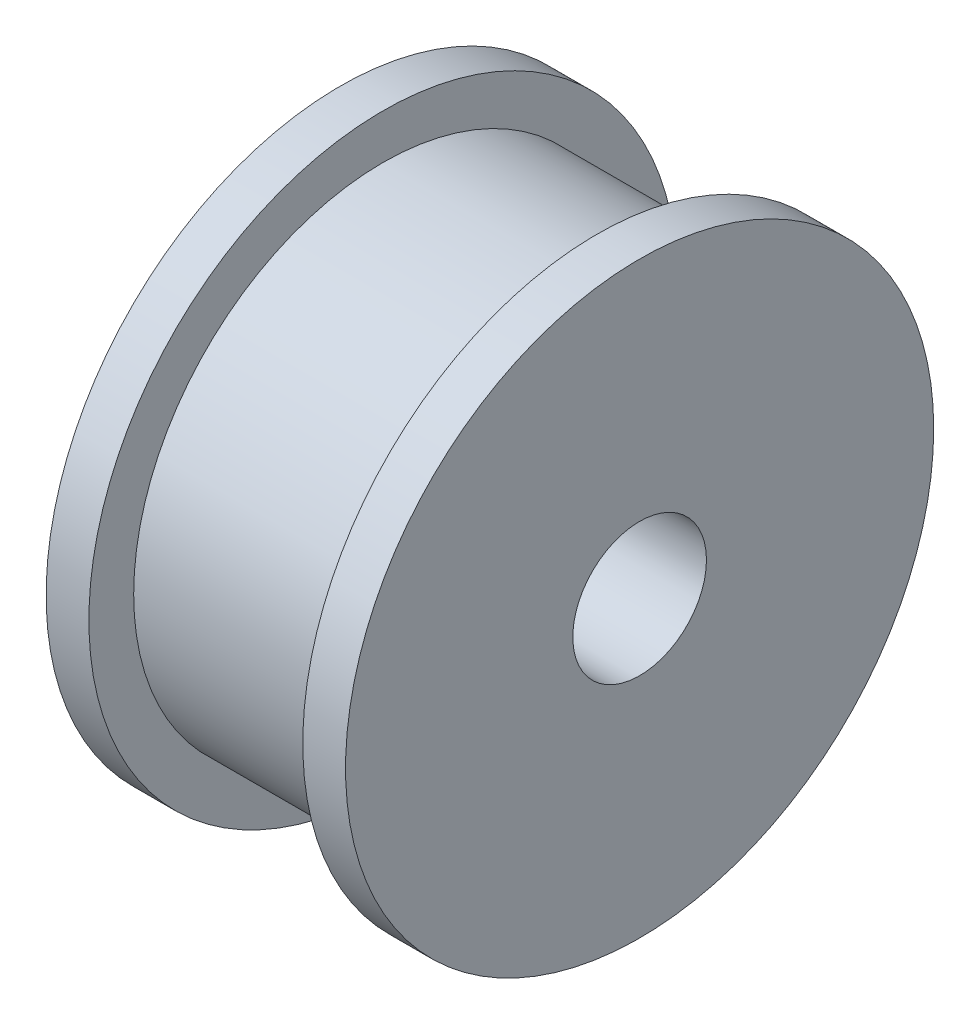
SolidWorks part; units mm, degrees
material "6061-T6 (SS)"
ref_plane "Front Plane" through (0, 0, 0) normal (0, 0, 1) x (1, 0, 0)
ref_plane "Top Plane" through (0, 0, 0) normal (0, 1, 0) x (1, 0, 0)
ref_plane "Right Plane" through (0, 0, 0) normal (1, 0, 0) x (0, 0, -1)
sketch "Sketch1" plane through (0, 0, 0) normal (0, 0, 1) x (1, 0, 0)
  line L1 (-5.6, 11) -> (-4, 11)
  line L2 (-4, 11) -> (-4, 9.325)
  line L3 (-4, 9.325) -> (4, 9.325)
  line L4 (4, 9.325) -> (4, 11)
  line L5 (4, 11) -> (5.6, 11)
  line L6 (5.6, 11) -> (5.6, 2.5)
  line L7 (5.6, 2.5) -> (-5.6, 2.5)
  line L8 (0, 0) -> (-7.6744, 0) construction
  line L9 (-5.6, 11) -> (-5.6, 2.5)
  line L11 (0, 9.325) -> (0, 2.5) construction
  dimension "D1" = 5
  dimension "D2" = 22
  dimension "D3" = 18.65
  dimension "D4" = 8
  dimension "D6" = 1.6
revolve "Revolve1" add sketch "Sketch1" angle 360 about L8
ref_axis "Axis1" through (-5.6, 0, 0) along (1, 0, 0)
